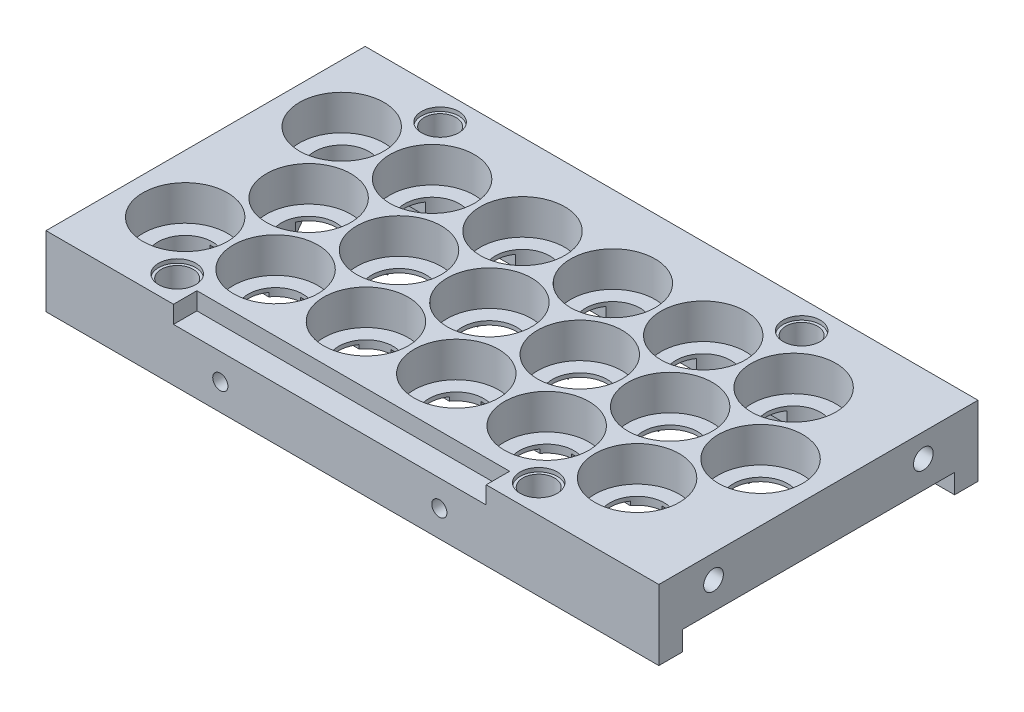
SolidWorks part; units mm, degrees
ref_plane "Front Plane" through (0, 0, 0) normal (0, 0, 1) x (1, 0, 0)
ref_plane "Top Plane" through (0, 0, 0) normal (0, 1, 0) x (1, 0, 0)
ref_plane "Right Plane" through (0, 0, 0) normal (1, 0, 0) x (0, 0, -1)
sketch "Sketch1" plane through (0, 0, 0) normal (0, 1, 0) x (1, 0, 0)
  line L0 (0, 0) -> (11.575, -20.0485) construction
  line L1 (11.575, -20.0485) -> (0, -40.097) construction
  line L2 (0, 0) -> (11.575, 0) construction
  line L3 (11.575, 0) -> (11.575, -20.0485) construction
  line L4 (11.575, -20.0485) -> (11.575, -40.097) construction
  line L5 (11.575, -40.097) -> (0, -40.097) construction
  line L6 (0, 0) -> (23.15, 0) construction
  line L7 (0, 0) -> (23.15, 0) construction
  line L8 (-14.825, -60.922) -> (142.15, -60.922)
  line L9 (-14.825, -60.922) -> (-14.825, 20.825)
  line L10 (-14.825, 20.825) -> (142.15, 20.825)
  line L11 (142.15, -60.922) -> (142.15, 20.825)
  circle A0 centre (0, 0) radius 10.825
  circle A1 centre (11.575, -20.0485) radius 10.825
  circle A2 centre (0, -40.097) radius 10.825
  circle A3 centre (23.15, 0) radius 10.825
  circle A4 centre (34.725, -20.0485) radius 10.825
  circle A5 centre (23.15, -40.097) radius 10.825
  circle A6 centre (46.3, 0) radius 10.825
  circle A7 centre (57.875, -20.0485) radius 10.825
  circle A8 centre (46.3, -40.097) radius 10.825
  circle A9 centre (69.45, 0) radius 10.825
  circle A10 centre (81.025, -20.0485) radius 10.825
  circle A11 centre (69.45, -40.097) radius 10.825
  circle A12 centre (92.6, 0) radius 10.825
  circle A13 centre (104.175, -20.0485) radius 10.825
  circle A14 centre (92.6, -40.097) radius 10.825
  circle A15 centre (115.75, 0) radius 10.825
  circle A16 centre (127.325, -20.0485) radius 10.825
  circle A17 centre (115.75, -40.097) radius 10.825
  circle A18 centre (0, 0) radius 7
  circle A19 centre (11.575, -20.0485) radius 7
  circle A20 centre (0, -40.097) radius 7
  circle A21 centre (23.15, 0) radius 7
  circle A22 centre (34.725, -20.0485) radius 7
  circle A23 centre (23.15, -40.097) radius 7
  circle A24 centre (46.3, 0) radius 7
  circle A25 centre (57.875, -20.0485) radius 7
  circle A26 centre (46.3, -40.097) radius 7
  circle A27 centre (69.45, 0) radius 7
  circle A28 centre (81.025, -20.0485) radius 7
  circle A29 centre (69.45, -40.097) radius 7
  circle A30 centre (92.6, 0) radius 7
  circle A31 centre (104.175, -20.0485) radius 7
  circle A32 centre (92.6, -40.097) radius 7
  circle A33 centre (115.75, 0) radius 7
  circle A34 centre (127.325, -20.0485) radius 7
  circle A35 centre (115.75, -40.097) radius 7
  dimension "D3" = 21.65
  dimension "D11" = 14
  dimension "D1" = 60
  dimension "D2" = 60
  dimension "D4" = 1.5
  dimension "D6" = 23.15
  dimension "D7" = 4
  dimension "D8" = 4
  dimension "D9" = 10
  dimension "D10" = 10
  dimension "D13" = 23.15
  dimension "D5" = 6
  dimension "D12" = 6
extrude "Boss-Extrude2" add sketch "Sketch1" along normal blind 11 contours L8 L11 L10 L9 A17 A16 A15 A14 A13 A12 A11 A10 A9 A8 A7 A6 A5 A4 A3 A2 A1 A0 region at (-13.0551, 0, 20.0485)
extrude "Boss-Extrude3" add sketch "Sketch1<3>" along normal blind 2 contours A0 A18 | A3 A21 | A6 A24 | A9 A27 | A12 A30 | A15 A33 | A1 A19 | A4 A22 | A7 A25 | A10 A28 | A13 A31 | A16 A34 | A17 A35 | A14 A32 | A11 A29 | A8 A26 | A5 A23 | A2 A20 region at (-10.5188, 0, 0) region at (1.0562, 0, 20.0485) region at (-10.5188, 0, 40.097) region at (12.6312, 0, 0) region at (24.2062, 0, 20.0485) region at (12.6312, 0, 40.097) region at (35.7812, 0, 0) region at (47.3562, 0, 20.0485) region at (35.7812, 0, 40.097) region at (58.9312, 0, 0) region at (70.5062, 0, 20.0485) region at (58.9312, 0, 40.097) region at (82.0812, 0, 0) region at (93.6562, 0, 20.0485) region at (82.0812, 0, 40.097) region at (105.2312, 0, 0) region at (116.8062, 0, 20.0485) region at (105.2312, 0, 40.097)
sketch "Sketch1<3>" plane through (0, 0, 0) normal (0, 1, 0) x (1, 0, 0) same geometry as "Sketch1"
sketch "Sketch2" plane through (0, 0, 0) normal (0, -1, 0) x (1, 0, 0)
  line L0 (0, 40.097) -> (11.575, 20.0485) construction
  line L1 (3.4641, 42.097) -> (15.0391, 22.0485)
  line L2 (-3.4641, 38.097) -> (8.1109, 18.0485)
  line L3 (11.575, 20.0485) -> (0, 0) construction
  line L4 (15.0391, 18.0485) -> (3.4641, -2)
  line L5 (8.1109, 22.0485) -> (-3.4641, 2)
  line L6 (19.6859, 38.097) -> (31.2609, 18.0485)
  line L7 (26.6141, 42.097) -> (38.1891, 22.0485)
  line L8 (31.2609, 22.0485) -> (19.6859, 2)
  line L9 (38.1891, 18.0485) -> (26.6141, -2)
  line L10 (23.15, 40.097) -> (34.725, 20.0485) construction
  line L11 (34.725, 20.0485) -> (23.15, 0) construction
  line L12 (42.8359, 38.097) -> (54.4109, 18.0485)
  line L13 (49.7641, 42.097) -> (61.3391, 22.0485)
  line L14 (54.4109, 22.0485) -> (42.8359, 2)
  line L15 (61.3391, 18.0485) -> (49.7641, -2)
  line L16 (46.3, 40.097) -> (57.875, 20.0485) construction
  line L17 (57.875, 20.0485) -> (46.3, 0) construction
  line L18 (65.9859, 38.097) -> (77.5609, 18.0485)
  line L19 (72.9141, 42.097) -> (84.4891, 22.0485)
  line L20 (77.5609, 22.0485) -> (65.9859, 2)
  line L21 (84.4891, 18.0485) -> (72.9141, -2)
  line L22 (69.45, 40.097) -> (81.025, 20.0485) construction
  line L23 (81.025, 20.0485) -> (69.45, 0) construction
  line L24 (89.1359, 38.097) -> (100.7109, 18.0485)
  line L25 (96.0641, 42.097) -> (107.6391, 22.0485)
  line L26 (100.7109, 22.0485) -> (89.1359, 2)
  line L27 (107.6391, 18.0485) -> (96.0641, -2)
  line L28 (92.6, 40.097) -> (104.175, 20.0485) construction
  line L29 (104.175, 20.0485) -> (92.6, 0) construction
  line L30 (112.2859, 38.097) -> (123.8609, 18.0485)
  line L31 (119.2141, 42.097) -> (130.7891, 22.0485)
  line L32 (123.8609, 22.0485) -> (112.2859, 2)
  line L33 (130.7891, 18.0485) -> (119.2141, -2)
  line L34 (115.75, 40.097) -> (127.325, 20.0485) construction
  line L35 (127.325, 20.0485) -> (115.75, 0) construction
  line L36 (-3.4641, 38.097) -> (19.6859, 38.097) construction
  line L37 (0, 40.097) -> (115.75, 40.097) construction
  line L38 (0, 44.097) -> (115.75, 44.097)
  line L39 (0, 36.097) -> (115.75, 36.097)
  line L40 (11.575, 20.0485) -> (127.325, 20.0485) construction
  line L41 (11.575, 24.0485) -> (127.325, 24.0485)
  line L42 (11.575, 16.0485) -> (127.325, 16.0485)
  line L43 (0, 0) -> (115.75, 0) construction
  line L44 (0, 4) -> (115.75, 4)
  line L45 (0, -4) -> (115.75, -4)
  arc A0 (3.4641, 42.097) -> (-3.4641, 38.097) centre (0, 40.097) ccw
  arc A1 (8.1109, 18.0485) -> (15.0391, 22.0485) centre (11.575, 20.0485) ccw
  arc A2 (15.0391, 18.0485) -> (8.1109, 22.0485) centre (11.575, 20.0485) ccw
  arc A3 (-3.4641, 2) -> (3.4641, -2) centre (0, 0) ccw
  arc A4 (26.6141, 42.097) -> (19.6859, 38.097) centre (23.15, 40.097) ccw
  arc A5 (31.2609, 18.0485) -> (38.1891, 22.0485) centre (34.725, 20.0485) ccw
  arc A6 (38.1891, 18.0485) -> (31.2609, 22.0485) centre (34.725, 20.0485) ccw
  arc A7 (19.6859, 2) -> (26.6141, -2) centre (23.15, 0) ccw
  arc A8 (49.7641, 42.097) -> (42.8359, 38.097) centre (46.3, 40.097) ccw
  arc A9 (54.4109, 18.0485) -> (61.3391, 22.0485) centre (57.875, 20.0485) ccw
  arc A10 (61.3391, 18.0485) -> (54.4109, 22.0485) centre (57.875, 20.0485) ccw
  arc A11 (42.8359, 2) -> (49.7641, -2) centre (46.3, 0) ccw
  arc A12 (72.9141, 42.097) -> (65.9859, 38.097) centre (69.45, 40.097) ccw
  arc A13 (77.5609, 18.0485) -> (84.4891, 22.0485) centre (81.025, 20.0485) ccw
  arc A14 (84.4891, 18.0485) -> (77.5609, 22.0485) centre (81.025, 20.0485) ccw
  arc A15 (65.9859, 2) -> (72.9141, -2) centre (69.45, 0) ccw
  arc A16 (96.0641, 42.097) -> (89.1359, 38.097) centre (92.6, 40.097) ccw
  arc A17 (100.7109, 18.0485) -> (107.6391, 22.0485) centre (104.175, 20.0485) ccw
  arc A18 (107.6391, 18.0485) -> (100.7109, 22.0485) centre (104.175, 20.0485) ccw
  arc A19 (89.1359, 2) -> (96.0641, -2) centre (92.6, 0) ccw
  arc A20 (119.2141, 42.097) -> (112.2859, 38.097) centre (115.75, 40.097) ccw
  arc A21 (123.8609, 18.0485) -> (130.7891, 22.0485) centre (127.325, 20.0485) ccw
  arc A22 (130.7891, 18.0485) -> (123.8609, 22.0485) centre (127.325, 20.0485) ccw
  arc A23 (112.2859, 2) -> (119.2141, -2) centre (115.75, 0) ccw
  arc A24 (0, 44.097) -> (0, 36.097) centre (0, 40.097) ccw
  arc A25 (115.75, 36.097) -> (115.75, 44.097) centre (115.75, 40.097) ccw
  arc A26 (11.575, 24.0485) -> (11.575, 16.0485) centre (11.575, 20.0485) ccw
  arc A27 (127.325, 16.0485) -> (127.325, 24.0485) centre (127.325, 20.0485) ccw
  arc A28 (0, 4) -> (0, -4) centre (0, 0) ccw
  arc A29 (115.75, -4) -> (115.75, 4) centre (115.75, 0) ccw
  point P3 (5.7875, 30.0727)
  point P8 (5.7875, 10.0242)
  point P18 (28.9375, 30.0727)
  point P25 (28.9375, 10.0242)
  point P34 (52.0875, 30.0727)
  point P39 (52.0875, 10.0242)
  point P48 (75.2375, 30.0727)
  point P53 (75.2375, 10.0242)
  point P62 (98.3875, 30.0727)
  point P67 (98.3875, 10.0242)
  point P76 (121.5375, 30.0727)
  point P81 (121.5375, 10.0242)
  point P91 (57.875, 40.097)
  point P96 (69.45, 20.0485)
  point P103 (57.875, 0)
  circle M62 centre (0, 0) radius 7
  circle M63 centre (23.15, 0) radius 7
  circle M64 centre (46.3, 0) radius 7
  circle M65 centre (69.45, 0) radius 7
  circle M66 centre (92.6, 0) radius 7
  circle M67 centre (115.75, 0) radius 7
  circle M68 centre (11.575, 20.0485) radius 7
  circle M69 centre (34.725, 20.0485) radius 7
  circle M70 centre (57.875, 20.0485) radius 7
  circle M71 centre (81.025, 20.0485) radius 7
  circle M72 centre (104.175, 20.0485) radius 7
  circle M73 centre (127.325, 20.0485) radius 7
  circle M74 centre (115.75, 40.097) radius 7
  circle M75 centre (92.6, 40.097) radius 7
  circle M76 centre (69.45, 40.097) radius 7
  circle M77 centre (46.3, 40.097) radius 7
  circle M78 centre (23.15, 40.097) radius 7
  circle M79 centre (0, 40.097) radius 7
  dimension "D1" = 8
  dimension "D3" = 23.15
  dimension "D4" = 8
  dimension "D5" = 8
  dimension "D6" = 8
extrude "Cut-Extrude1" cut sketch "Sketch2" against normal blind 1 contours L1 L39 L38 M78 M79 | L7 L39 L38 M77 M78 | L39 L2 L1 M79 M68 | L42 L8 L6 L41 M68 M69 | L6 L41 L7 L39 M69 M78 | L12 L41 L13 L39 M70 M77 | L13 L39 L38 M76 M77 | L18 L41 L19 L39 M71 M76 | L19 L39 L38 M75 M76 | L24 L41 L25 L39 M72 M75 | L25 L39 L38 M74 M75 | L30 L41 L31 M73 M74 | L42 L32 L30 L41 M72 M73 | L42 L26 L24 L41 M71 M72 | L42 L20 L18 L41 M70 M71 | L42 L14 L12 L41 M69 M70 | L45 L44 L4 M62 M63 | L44 L4 L5 M62 M68 | L45 L44 L9 M63 M64 | L45 L44 L15 M64 M65 | L45 L44 L21 M65 M66 | L45 L44 L27 M66 M67 | L44 L27 L42 L26 M66 M72 | L42 L32 L33 M67 M73 | L44 L21 L42 L20 M65 M71 | L44 L15 L42 L14 M64 M70 | L39 L13 M77 | L39 L25 M75 | L39 L19 M76 | L41 L6 M69 | L44 L4 M62 | L44 L15 M64 | L44 L21 M65 | L44 L27 M66 | L41 L30 M73 | L32 L42 M73 | L41 L24 M72 | L26 L42 M72 | L41 L18 M71 | L20 L42 M71 | L41 L12 M70 | L14 L42 M70 | L44 L9 L42 L8 M63 M69 | L8 L42 M69 | L39 L7 M78 | L39 L1 M79 | L44 A29 L45 A28 region at (11.6138, 0, 40.1242) region at (6.3461, 0, 36.4331) region at (5.7834, 0, 30.0255) region at (23.0718, 0, 20.0485) region at (28.9375, 0, 30.0727) region at (34.7638, 0, 40.1242) region at (28.3789, 0, 23.7124) region at (5.7834, 0, 10.0715) region at (29.4961, 0, 36.4331) region at (57.9138, 0, 40.1242) region at (28.3789, 0, 16.3846) region at (28.9375, 0, 10.0242) region at (6.3461, 0, 3.6639) region at (11.6138, 0, -0.0272) region at (52.0875, 0, 30.0727) region at (46.2218, 0, 20.0485) region at (52.6461, 0, 36.4331) region at (81.0638, 0, 40.1242) region at (51.5289, 0, 23.7124) region at (34.7638, 0, -0.0272) region at (75.2375, 0, 30.0727) region at (75.7961, 0, 36.4331) region at (104.2138, 0, 40.1242) region at (74.6789, 0, 23.7124) region at (69.3718, 0, 20.0485) region at (51.5289, 0, 16.3846) region at (52.0875, 0, 10.0242) region at (57.9138, 0, -0.0272) region at (98.3875, 0, 30.0727) region at (98.9461, 0, 36.4331) region at (97.8289, 0, 23.7124) region at (92.5218, 0, 20.0485) region at (74.6789, 0, 16.3846) region at (52.6461, 0, 3.6639) region at (81.0638, 0, -0.0272) region at (121.5416, 0, 30.12) region at (75.2375, 0, 10.0242) region at (120.9789, 0, 23.7124) region at (115.6718, 0, 20.0485) region at (97.8289, 0, 16.3846) region at (75.7961, 0, 3.6639) region at (104.2138, 0, -0.0272) region at (98.3875, 0, 10.0242) region at (121.5416, 0, 9.977) region at (120.9789, 0, 16.3846) region at (98.9461, 0, 3.6639)
sketch "Sketch9" plane through (0, 11, 0) normal (0, 1, 0) x (1, 0, 0)
  line L0 (11.575, -60.922) -> (11.575, 20.825)
  line L1 (-14.825, 20.825) -> (142.15, 20.825) construction
  line L2 (104.175, 20.825) -> (104.175, -60.922)
  line L3 (-14.825, -60.922) -> (142.15, -60.922) construction
  circle A0 centre (11.575, 13.625) radius 4.0767
  circle A1 centre (11.575, -53.722) radius 4.0767
  circle A2 centre (104.175, -53.722) radius 4.0767
  circle A3 centre (104.175, 13.625) radius 4.0767
  point P0 (11.575, 13.625)
  point P7 (11.575, -20.0485)
  point P15 (104.175, -20.0485)
  point P20 (104.175, 13.625)
  point P21 (104.175, -53.722)
  point P22 (11.575, -53.722)
  dimension "D5" = 8.1534
  dimension "D1" = 7.2
  dimension "D4" = 7.2
extrude "Cut-Extrude3" cut sketch "Sketch9" against normal up to next contours A2 | A1 | A0 | A3
sketch "Sketch10" plane through (0, 11, 0) normal (0, 1, 0) x (1, 0, 0)
  circle A0 centre (11.575, 13.625) radius 4.7625
  circle A1 centre (104.175, 13.625) radius 4.7625
  circle A2 centre (104.175, -53.722) radius 4.7625
  circle A3 centre (11.575, -53.722) radius 4.7625
  dimension "D1" = 9.525
extrude "Cut-Extrude4" cut sketch "Sketch10" against normal blind 1
sketch "Sketch13" plane through (0, 0, 0) normal (0, -1, 0) x (1, 0, 0)
  line L0 (142.15, 60.922) -> (142.15, -20.825) construction
  line L5 (3.575, 53.722) -> (3.575, 60.922)
  line L8 (-14.825, 60.922) -> (142.15, 60.922) construction
  line L9 (3.575, 60.922) -> (19.575, 60.922)
  line L10 (19.575, 60.922) -> (19.575, 53.722)
  line L12 (57.875, 20.0485) -> (57.875, -20.825) construction
  line L13 (-14.825, -20.825) -> (142.15, -20.825) construction
  line L14 (11.575, 20.0485) -> (127.325, 20.0485) construction
  line L16 (96.175, 60.922) -> (96.175, 53.722)
  line L17 (112.175, 60.922) -> (96.175, 60.922)
  line L18 (112.175, 53.722) -> (112.175, 60.922)
  line L19 (-14.825, 60.922) -> (142.15, 60.922)
  line L20 (-14.825, 60.922) -> (-14.825, 54.922)
  line L21 (-14.825, 54.922) -> (142.15, 54.922)
  line L22 (142.15, 60.922) -> (142.15, 54.922)
  line L23 (142.15, -20.825) -> (142.15, -14.825)
  line L24 (-14.825, -14.825) -> (142.15, -14.825)
  line L25 (-14.825, -20.825) -> (-14.825, -14.825)
  line L26 (-14.825, -20.825) -> (142.15, -20.825)
  line L27 (112.175, -13.625) -> (112.175, -20.825)
  line L28 (112.175, -20.825) -> (96.175, -20.825)
  line L29 (96.175, -20.825) -> (96.175, -13.625)
  line L32 (19.575, -20.825) -> (19.575, -13.625)
  line L33 (3.575, -20.825) -> (19.575, -20.825)
  line L34 (3.575, -13.625) -> (3.575, -20.825)
  circle A4 centre (11.575, 53.722) radius 6.5
  circle A5 centre (11.575, 53.722) radius 8
  circle A6 centre (104.175, 53.722) radius 8
  circle A7 centre (104.175, 53.722) radius 6.5
  circle A8 centre (104.175, -13.625) radius 6.5
  circle A9 centre (104.175, -13.625) radius 8
  circle A10 centre (11.575, -13.625) radius 8
  circle A11 centre (11.575, -13.625) radius 6.5
  line M15 (142.15, 60.922) -> (-14.825, 60.922)
  line M16 (-14.825, 60.922) -> (-14.825, -20.825)
  line M17 (-14.825, -20.825) -> (142.15, -20.825)
  line M18 (142.15, -20.825) -> (142.15, 60.922)
  dimension "D1" = 13
  dimension "D2" = 16
  dimension "D3" = 6
extrude "Boss-Extrude7" add sketch "Sketch13" along normal blind 7 contours L21 L5 M16 M15 | A5 L5 L21 M15 | A5 L21 L10 M15 | L10 L21 L16 M15 | L21 A5 L19 A4 | A5 L21 A4 | L21 A6 L16 M15 | L21 A7 A6 L19 | L21 A7 A6 | A6 L21 L18 M15 | L18 L21 M18 M15 | A9 L24 L29 L26 | L28 A9 L24 A8 | A9 L26 L27 L24 | L24 L27 L26 M18 | L32 L26 L29 L24 | L24 A9 A8 | L34 L24 M16 M17 | L26 A10 L24 L34 | L24 A11 A10 | L24 A11 A10 L33 | L24 A10 L26 L32 region at (3.7817, 0, 54.3098) region at (-5.625, 0, 57.922) region at (4.8282, 0, 59.2567) region at (5.2714, 0, 58.3681) region at (18.3218, 0, 59.2567) region at (57.875, 0, 57.922) region at (-5.625, 0, -17.825) region at (97.4282, 0, 59.2567) region at (4.8282, 0, -19.1597) region at (96.3817, 0, 54.3098) region at (97.8714, 0, 58.3681) region at (3.7817, 0, -14.2128) region at (4.4261, 0, -14.9942) region at (110.9218, 0, 59.2567) region at (127.1625, 0, 57.922) region at (18.3218, 0, -19.1597) region at (57.875, 0, -17.825) region at (97.4282, 0, -19.1597) region at (127.1625, 0, -17.825) region at (96.3817, 0, -14.2128) region at (97.0261, 0, -14.9942) region at (110.9218, 0, -19.1597)
sketch "Sketch14" plane through (0, 0, 0) normal (0, -1, 0) x (1, 0, 0)
  line L2 (142.15, 54.922) -> (142.15, -14.825) construction
  line L4 (5.2386, 17.0736) -> (-0.5918, 6.9749) construction
  line L5 (5.7446, -4) -> (17.4054, -4) construction
  line L6 (28.8946, -4) -> (40.5554, -4) construction
  line L7 (52.0446, -4) -> (63.7054, -4) construction
  line L8 (75.1946, -4) -> (86.8554, -4) construction
  line L9 (98.3446, -4) -> (110.0054, -4) construction
  line L10 (127.9168, 13.0736) -> (122.0864, 2.9749) construction
  line L11 (122.0864, 37.122) -> (127.9168, 27.0234) construction
  line L12 (98.3446, 44.097) -> (110.0054, 44.097) construction
  line L13 (75.1946, 44.097) -> (86.8554, 44.097) construction
  line L14 (52.0446, 44.097) -> (63.7054, 44.097) construction
  line L15 (28.8946, 44.097) -> (40.5554, 44.097) construction
  line L16 (-0.5918, 33.122) -> (5.2386, 23.0234) construction
  line L17 (5.7446, 44.097) -> (17.4054, 44.097) construction
  line L20 (142.15, 54.922) -> (142.15, -14.825)
  line L22 (5.2386, 17.0736) -> (-0.5918, 6.9749)
  line L23 (5.7446, -4) -> (17.4054, -4)
  line L24 (28.8946, -4) -> (40.5554, -4)
  line L25 (52.0446, -4) -> (63.7054, -4)
  line L26 (75.1946, -4) -> (86.8554, -4)
  line L27 (98.3446, -4) -> (110.0054, -4)
  line L28 (127.9168, 13.0736) -> (122.0864, 2.9749)
  line L29 (122.0864, 37.122) -> (127.9168, 27.0234)
  line L30 (98.3446, 44.097) -> (110.0054, 44.097)
  line L31 (75.1946, 44.097) -> (86.8554, 44.097)
  line L32 (52.0446, 44.097) -> (63.7054, 44.097)
  line L33 (28.8946, 44.097) -> (40.5554, 44.097)
  line L34 (-0.5918, 33.122) -> (5.2386, 23.0234)
  line L35 (5.7446, 44.097) -> (17.4054, 44.097)
  line L36 (112.0845, -14.825) -> (142.15, -14.825) construction
  line L37 (19.4845, -14.825) -> (96.2655, -14.825) construction
  line L38 (-14.825, -14.825) -> (3.6655, -14.825) construction
  line L39 (-14.825, 54.922) -> (-14.825, -14.825) construction
  line L40 (112.0845, 54.922) -> (142.15, 54.922) construction
  line L41 (19.4845, 54.922) -> (96.2655, 54.922) construction
  line L42 (-14.825, 54.922) -> (3.6655, 54.922) construction
  line L43 (112.0845, -14.825) -> (142.15, -14.825)
  line L44 (19.4845, -14.825) -> (96.2655, -14.825)
  line L45 (-14.825, -14.825) -> (3.6655, -14.825)
  line L46 (-14.825, 54.922) -> (-14.825, -14.825)
  line L47 (112.0845, 54.922) -> (142.15, 54.922)
  line L48 (19.4845, 54.922) -> (96.2655, 54.922)
  line L49 (-14.825, 54.922) -> (3.6655, 54.922)
  arc A3 (5.2386, 23.0234) -> (5.2386, 17.0736) centre (11.575, 20.0485) ccw construction
  arc A4 (-0.5918, 6.9749) -> (5.7446, -4) centre (0, 0) ccw construction
  arc A5 (17.4054, -4) -> (28.8946, -4) centre (23.15, 0) ccw construction
  arc A6 (40.5554, -4) -> (52.0446, -4) centre (46.3, 0) ccw construction
  arc A7 (63.7054, -4) -> (75.1946, -4) centre (69.45, 0) ccw construction
  arc A8 (86.8554, -4) -> (98.3446, -4) centre (92.6, 0) ccw construction
  arc A9 (110.0054, -4) -> (122.0864, 2.9749) centre (115.75, 0) ccw construction
  arc A10 (127.9168, 13.0736) -> (127.9168, 27.0234) centre (127.325, 20.0485) ccw construction
  arc A11 (122.0864, 37.122) -> (110.0054, 44.097) centre (115.75, 40.097) ccw construction
  arc A12 (98.3446, 44.097) -> (86.8554, 44.097) centre (92.6, 40.097) ccw construction
  arc A13 (75.1946, 44.097) -> (63.7054, 44.097) centre (69.45, 40.097) ccw construction
  arc A14 (52.0446, 44.097) -> (40.5554, 44.097) centre (46.3, 40.097) ccw construction
  arc A16 (28.8946, 44.097) -> (17.4054, 44.097) centre (23.15, 40.097) ccw construction
  arc A17 (5.7446, 44.097) -> (-0.5918, 33.122) centre (0, 40.097) ccw construction
  arc A21 (5.2386, 23.0234) -> (5.2386, 17.0736) centre (11.575, 20.0485) ccw
  arc A22 (-0.5918, 6.9749) -> (5.7446, -4) centre (0, 0) ccw
  arc A23 (17.4054, -4) -> (28.8946, -4) centre (23.15, 0) ccw
  arc A24 (40.5554, -4) -> (52.0446, -4) centre (46.3, 0) ccw
  arc A25 (63.7054, -4) -> (75.1946, -4) centre (69.45, 0) ccw
  arc A26 (86.8554, -4) -> (98.3446, -4) centre (92.6, 0) ccw
  arc A27 (110.0054, -4) -> (122.0864, 2.9749) centre (115.75, 0) ccw
  arc A28 (127.9168, 13.0736) -> (127.9168, 27.0234) centre (127.325, 20.0485) ccw
  arc A29 (122.0864, 37.122) -> (110.0054, 44.097) centre (115.75, 40.097) ccw
  arc A30 (98.3446, 44.097) -> (86.8554, 44.097) centre (92.6, 40.097) ccw
  arc A31 (75.1946, 44.097) -> (63.7054, 44.097) centre (69.45, 40.097) ccw
  arc A32 (52.0446, 44.097) -> (40.5554, 44.097) centre (46.3, 40.097) ccw
  arc A34 (28.8946, 44.097) -> (17.4054, 44.097) centre (23.15, 40.097) ccw
  arc A35 (5.7446, 44.097) -> (-0.5918, 33.122) centre (0, 40.097) ccw
  arc A36 (112.0845, -14.825) -> (96.2655, -14.825) centre (104.175, -13.625) ccw construction
  arc A37 (19.4845, -14.825) -> (3.6655, -14.825) centre (11.575, -13.625) ccw construction
  arc A38 (96.2655, 54.922) -> (112.0845, 54.922) centre (104.175, 53.722) ccw construction
  arc A39 (3.6655, 54.922) -> (19.4845, 54.922) centre (11.575, 53.722) ccw construction
  arc A40 (112.0845, -14.825) -> (96.2655, -14.825) centre (104.175, -13.625) ccw
  arc A41 (19.4845, -14.825) -> (3.6655, -14.825) centre (11.575, -13.625) ccw
  arc A42 (96.2655, 54.922) -> (112.0845, 54.922) centre (104.175, 53.722) ccw
  arc A43 (3.6655, 54.922) -> (19.4845, 54.922) centre (11.575, 53.722) ccw
extrude "Boss-Extrude9" add sketch "Sketch14" along normal blind 2
sketch "Sketch16" plane through (0, 0, 0) normal (0, -1, 0) x (1, 0, 0)
  line L0 (17.4054, 36.097) -> (12.1668, 27.0234) construction
  line L1 (12.1668, 27.0234) -> (17.3196, 24.0485) construction
  line L2 (17.3196, 24.0485) -> (22.5582, 33.122) construction
  line L3 (22.5582, 33.122) -> (17.4054, 36.097) construction
  line L4 (14.7861, 31.5602) -> (19.9389, 28.5853) construction
  line L5 (15.5361, 32.8592) -> (20.6889, 29.8843)
  line L6 (14.0361, 30.2612) -> (19.1889, 27.2862)
  line L7 (11.575, 20.0485) -> (126.446, 20.0485) construction
  line L8 (40.5554, 36.097) -> (35.3168, 27.0234) construction
  line L9 (35.3168, 27.0234) -> (40.4696, 24.0485) construction
  line L10 (40.4696, 24.0485) -> (45.7082, 33.122) construction
  line L11 (45.7082, 33.122) -> (40.5554, 36.097) construction
  line L12 (37.9361, 31.5602) -> (43.0889, 28.5853) construction
  line L13 (38.6861, 32.8592) -> (43.8389, 29.8843)
  line L14 (37.1861, 30.2612) -> (42.3389, 27.2862)
  line L15 (63.7054, 36.097) -> (58.4668, 27.0234) construction
  line L16 (58.4668, 27.0234) -> (63.6196, 24.0485) construction
  line L17 (63.6196, 24.0485) -> (68.8582, 33.122) construction
  line L18 (68.8582, 33.122) -> (63.7054, 36.097) construction
  line L19 (61.0861, 31.5602) -> (66.2389, 28.5853) construction
  line L20 (61.8361, 32.8592) -> (66.9889, 29.8843)
  line L21 (60.3361, 30.2612) -> (65.4889, 27.2862)
  line L22 (86.8554, 36.097) -> (81.6168, 27.0234) construction
  line L23 (81.6168, 27.0234) -> (86.7696, 24.0485) construction
  line L24 (86.7696, 24.0485) -> (92.0082, 33.122) construction
  line L25 (92.0082, 33.122) -> (86.8554, 36.097) construction
  line L26 (84.2361, 31.5602) -> (89.3889, 28.5853) construction
  line L27 (84.9861, 32.8592) -> (90.1389, 29.8843)
  line L28 (83.4861, 30.2612) -> (88.6389, 27.2862)
  line L29 (110.0054, 36.097) -> (104.7668, 27.0234) construction
  line L30 (104.7668, 27.0234) -> (109.9196, 24.0485) construction
  line L31 (109.9196, 24.0485) -> (115.1582, 33.122) construction
  line L32 (115.1582, 33.122) -> (110.0054, 36.097) construction
  line L33 (107.3861, 31.5602) -> (112.5389, 28.5853) construction
  line L34 (108.1361, 32.8592) -> (113.2889, 29.8843)
  line L35 (106.6361, 30.2612) -> (111.7889, 27.2862)
  line L36 (14.7861, 8.5368) -> (19.9389, 11.5117) construction
  line L37 (15.5361, 7.2377) -> (20.6889, 10.2127)
  line L38 (14.0361, 9.8358) -> (19.1889, 12.8108)
  line L39 (37.9361, 8.5368) -> (43.0889, 11.5117) construction
  line L40 (38.6861, 7.2377) -> (43.8389, 10.2127)
  line L41 (37.1861, 9.8358) -> (42.3389, 12.8108)
  line L42 (61.0861, 8.5368) -> (66.2389, 11.5117) construction
  line L43 (61.8361, 7.2377) -> (66.9889, 10.2127)
  line L44 (60.3361, 9.8358) -> (65.4889, 12.8108)
  line L45 (84.2361, 8.5368) -> (89.3889, 11.5117) construction
  line L46 (84.9861, 7.2377) -> (90.1389, 10.2127)
  line L47 (83.4861, 9.8358) -> (88.6389, 12.8108)
  line L48 (107.3861, 8.5368) -> (112.5389, 11.5117) construction
  line L49 (108.1361, 7.2377) -> (113.2889, 10.2127)
  line L50 (106.6361, 9.8358) -> (111.7889, 12.8108)
  line L51 (115.1582, 6.9749) -> (110.0054, 4) construction
  line L52 (109.9196, 16.0485) -> (115.1582, 6.9749) construction
  line L53 (104.7668, 13.0736) -> (109.9196, 16.0485) construction
  line L54 (110.0054, 4) -> (104.7668, 13.0736) construction
  line L55 (92.0082, 6.9749) -> (86.8554, 4) construction
  line L56 (86.7696, 16.0485) -> (92.0082, 6.9749) construction
  line L57 (81.6168, 13.0736) -> (86.7696, 16.0485) construction
  line L58 (86.8554, 4) -> (81.6168, 13.0736) construction
  line L59 (68.8582, 6.9749) -> (63.7054, 4) construction
  line L60 (63.6196, 16.0485) -> (68.8582, 6.9749) construction
  line L61 (58.4668, 13.0736) -> (63.6196, 16.0485) construction
  line L62 (63.7054, 4) -> (58.4668, 13.0736) construction
  line L63 (45.7082, 6.9749) -> (40.5554, 4) construction
  line L64 (40.4696, 16.0485) -> (45.7082, 6.9749) construction
  line L65 (35.3168, 13.0736) -> (40.4696, 16.0485) construction
  line L66 (40.5554, 4) -> (35.3168, 13.0736) construction
  line L67 (22.5582, 6.9749) -> (17.4054, 4) construction
  line L68 (17.3196, 16.0485) -> (22.5582, 6.9749) construction
  line L69 (12.1668, 13.0736) -> (17.3196, 16.0485) construction
  line L70 (17.4054, 4) -> (12.1668, 13.0736) construction
  arc A0 (15.5361, 32.8592) -> (14.0361, 30.2612) centre (14.7861, 31.5602) ccw
  arc A1 (19.1889, 27.2862) -> (20.6889, 29.8843) centre (19.9389, 28.5853) ccw
  arc A2 (38.6861, 32.8592) -> (37.1861, 30.2612) centre (37.9361, 31.5602) ccw
  arc A3 (42.3389, 27.2862) -> (43.8389, 29.8843) centre (43.0889, 28.5853) ccw
  arc A4 (61.8361, 32.8592) -> (60.3361, 30.2612) centre (61.0861, 31.5602) ccw
  arc A5 (65.4889, 27.2862) -> (66.9889, 29.8843) centre (66.2389, 28.5853) ccw
  arc A6 (84.9861, 32.8592) -> (83.4861, 30.2612) centre (84.2361, 31.5602) ccw
  arc A7 (88.6389, 27.2862) -> (90.1389, 29.8843) centre (89.3889, 28.5853) ccw
  arc A8 (108.1361, 32.8592) -> (106.6361, 30.2612) centre (107.3861, 31.5602) ccw
  arc A9 (111.7889, 27.2862) -> (113.2889, 29.8843) centre (112.5389, 28.5853) ccw
  arc A10 (40.5554, 36.097) -> (45.7082, 33.122) centre (46.3, 40.097) ccw construction
  arc A11 (15.5361, 7.2377) -> (14.0361, 9.8358) centre (14.7861, 8.5368) cw
  arc A12 (19.1889, 12.8108) -> (20.6889, 10.2127) centre (19.9389, 11.5117) cw
  arc A13 (38.6861, 7.2377) -> (37.1861, 9.8358) centre (37.9361, 8.5368) cw
  arc A14 (42.3389, 12.8108) -> (43.8389, 10.2127) centre (43.0889, 11.5117) cw
  arc A15 (61.8361, 7.2377) -> (60.3361, 9.8358) centre (61.0861, 8.5368) cw
  arc A16 (65.4889, 12.8108) -> (66.9889, 10.2127) centre (66.2389, 11.5117) cw
  arc A17 (84.9861, 7.2377) -> (83.4861, 9.8358) centre (84.2361, 8.5368) cw
  arc A18 (88.6389, 12.8108) -> (90.1389, 10.2127) centre (89.3889, 11.5117) cw
  arc A19 (108.1361, 7.2377) -> (106.6361, 9.8358) centre (107.3861, 8.5368) cw
  arc A20 (111.7889, 12.8108) -> (113.2889, 10.2127) centre (112.5389, 11.5117) cw
  point P10 (17.3625, 30.0727)
  point P25 (40.5125, 30.0727)
  point P36 (63.6625, 30.0727)
  point P47 (86.8125, 30.0727)
  point P58 (109.9625, 30.0727)
  point P68 (17.3625, 10.0242)
  point P75 (40.5125, 10.0242)
  point P82 (63.6625, 10.0242)
  point P89 (86.8125, 10.0242)
  point P96 (109.9625, 10.0242)
  dimension "D1" = 1.5
  dimension "D2" = 5
extrude "Boss-Extrude10" add sketch "Sketch16" along normal blind 2
sketch "Sketch17" plane through (0, -2, 0) normal (0, -1, 0) x (-1, 0, 0)
  line L0 (-57.875, -44.097) -> (-57.875, -54.922) construction
  line L1 (-63.7054, -44.097) -> (-52.0446, -44.097) construction
  line L2 (-19.4845, -54.922) -> (-96.2655, -54.922) construction
  line L3 (-142.15, 14.825) -> (-142.15, -54.922) construction
  line L4 (14.825, -54.922) -> (14.825, 14.825) construction
  line L5 (8.825, -49.5095) -> (-57.875, -49.5095) construction
  line L6 (-57.875, -49.5095) -> (-132.15, -49.5095) construction
  line L7 (-127.325, -20.0485) -> (-11.575, -20.0485)
  line L8 (-57.875, 9.4125) -> (-132.15, 9.4125) construction
  line L9 (8.825, 9.4125) -> (-57.875, 9.4125) construction
  line L10 (-57.875, 4) -> (-57.875, 14.825) construction
  circle A0 centre (8.825, -49.5095) radius 1.9431
  circle A1 centre (-57.875, -49.5095) radius 1.9431
  circle A2 centre (-132.15, -49.5095) radius 1.9431
  circle A3 centre (-132.15, 9.4125) radius 1.9431
  circle A4 centre (-57.875, 9.4125) radius 1.9431
  circle A5 centre (8.825, 9.4125) radius 1.9431
  dimension "D3" = 6
  dimension "D1" = 3.8862
  dimension "D2" = 10
extrude "Cut-Extrude5" cut sketch "Sketch17" against normal blind 4 contours A3 | A2 | A4 | A5 | A0 | A1 region at (-8.825, -2, 49.5095) region at (57.875, -2, 49.5095) region at (132.15, -2, 49.5095) region at (132.15, -2, -9.4125) region at (57.875, -2, -9.4125) region at (-8.825, -2, -9.4125)
sketch "Sketch19" plane through (0, 0, 60.922) normal (0, 0, 1) x (1, 0, 0)
  line L0 (11.575, 11) -> (104.175, 11)
  line L1 (-14.825, 11) -> (142.15, 11) construction
  line L2 (97.925, 11) -> (17.825, 11)
  line L3 (17.825, 11) -> (97.925, 11)
  line L4 (17.825, 11) -> (17.825, 6.525)
  line L5 (97.925, 11) -> (97.925, 6.525)
  line L6 (17.825, 6.525) -> (97.925, 6.525)
  point P5 (57.875, 11)
  point P9 (57.875, 11)
  dimension "D1" = 92.6
  dimension "D2" = 26.4
  dimension "D3" = 80.1
  dimension "D4" = 4.475
extrude "Cut-Extrude6" cut sketch "Sketch19" against normal blind 6 contours L4 L6 L5 L0 region at (57.875, 8.7625, 60.922)
sketch "Sketch20" plane through (0, 0, 60.922) normal (0, 0, 1) x (1, 0, 0)
  line L0 (29.825, 6.525) -> (85.925, 6.525)
  line L1 (29.825, 6.525) -> (29.825, -0.2375)
  line L2 (85.925, 6.525) -> (85.925, -0.2375)
  line L3 (29.825, -0.2375) -> (85.925, -0.2375)
  line L4 (29.825, 6.525) -> (17.825, 6.525) construction
  line L5 (85.925, 6.525) -> (97.925, 6.525) construction
  line L6 (57.875, 6.525) -> (57.875, -7)
  line L9 (142.15, -7) -> (-14.825, -7) construction
  circle A0 centre (29.825, -0.2375) radius 1.9431
  circle A1 centre (85.925, -0.2375) radius 1.9431
  point P9 (57.875, -0.2375)
  dimension "D2" = 3.8862
  dimension "D1" = 12
extrude "Cut-Extrude7" cut sketch "Sketch20" against normal blind 3.8862 contours L1 A0 L3 | L3 A0 L1 | L3 A1 L2 | L2 A1 L3 region at (30.6497, 0.5872, 60.922) region at (29.5501, -0.5124, 60.922) region at (86.1999, -0.5124, 60.922) region at (85.1003, 0.5872, 60.922)
sketch "Sketch22" plane through (142.15, 0, 0) normal (1, 0, 0) x (0, 0, -1)
  line L0 (-46.922, 5) -> (-60.922, 5)
  line L1 (-60.922, 11) -> (-60.922, -7) construction
  line L2 (6.825, 5) -> (20.825, 5)
  line L3 (20.825, 11) -> (20.825, -7) construction
  line L4 (-46.922, 5) -> (-46.922, 11)
  line L5 (-60.922, 11) -> (20.825, 11) construction
  line L6 (6.825, 5) -> (6.825, 11)
  circle A0 centre (-46.922, 5) radius 2.525
  circle A1 centre (6.825, 5) radius 2.525
  dimension "D1" = 5.05
  dimension "D2" = 14
  dimension "D3" = 6
extrude "Cut-Extrude8" cut sketch "Sketch22" against normal blind 3.81 contours L0 A0 L4 | L4 A0 L0 | L6 A1 L2 | L2 A1 L6 region at (142.15, 4.6428, 46.5648) region at (142.15, 6.0716, 47.9936) region at (142.15, 6.0716, -7.8966) region at (142.15, 4.6428, -6.4678)
equation "\"hole_diameter\"= 21.65"
equation "\"D3@Sketch1\"=\"hole_diameter\""
equation "\"cell_spacing\"= 1.5"
equation "\"D4@Sketch1\"=\"cell_spacing\""
equation "\"D6@Sketch1\"=\"hole_diameter\"+\"cell_spacing\""
equation "\"len_spacing\"= 4"
equation "\"D7@Sketch1\"=\"len_spacing\""
equation "\"D8@Sketch1\"=\"len_spacing\""
equation "\"wid_spacing\"= 10"
equation "\"D9@Sketch1\"=\"wid_spacing\""
equation "\"D10@Sketch1\"=\"wid_spacing\""
equation "\"nipple\"= 14"
equation "\"D11@Sketch1\"=\"nipple\""
equation "\"D13@Sketch1\"=\"hole_diameter\"+\"cell_spacing\""
equation "\"channel\"= 8"
equation "\"D1@Sketch2\"=\"channel\""
equation "\"D3@Sketch2\"=\"hole_diameter\"+\"cell_spacing\""
equation "\"D4@Sketch2\"=\"channel\""
equation "\"D5@Sketch2\"=\"channel\""
equation "\"D6@Sketch2\"=\"channel\""
equation "\"lip\"= 6"
equation "\"lip_height\"= 1"
equation "\"outer_fillet\"=6"
equation "\"insert_placement\"= 7.2"
equation "\"D4@Sketch9\"=\"insert_placement\""
equation "\"D1@Sketch9\"=\"insert_placement\""
equation "\"heat_insert_diameter\"=8.1534"
equation "\"D5@Sketch9\"=\"heat_insert_diameter\""
equation "\"heat_insert_lip_diameter\"=9.525"
equation "\"D1@Sketch10\"=\"heat_insert_lip_diameter\""
equation "\"bolt_head_diameter\"=13"
equation "\"D1@Sketch13\"=\"bolt_head_diameter\""
equation "\"D2@Sketch13\"=\"bolt_head_diameter\"+3"
equation "\"D3@Sketch13\"=\"lip\""
equation "\"small_heat_insert\"= .153in"
equation "\"D1@Sketch17\"=\"small_heat_insert\""
equation "\"bdm_cut_depth\"=6"
equation "\"D1@Cut-Extrude6\"=\"bdm_cut_depth\""
equation "\"D1@Cut-Extrude7\"=\"small_heat_insert\""
equation "\"D2@Sketch20\"=\"small_heat_insert\""
equation "\"heat_insert_depth\"= .15in"
equation "\"D1@Cut-Extrude8\"=\"heat_insert_depth\""
equation "\"heat_insert_space\"=6"
equation "\"heat_insert\"=5.5"
